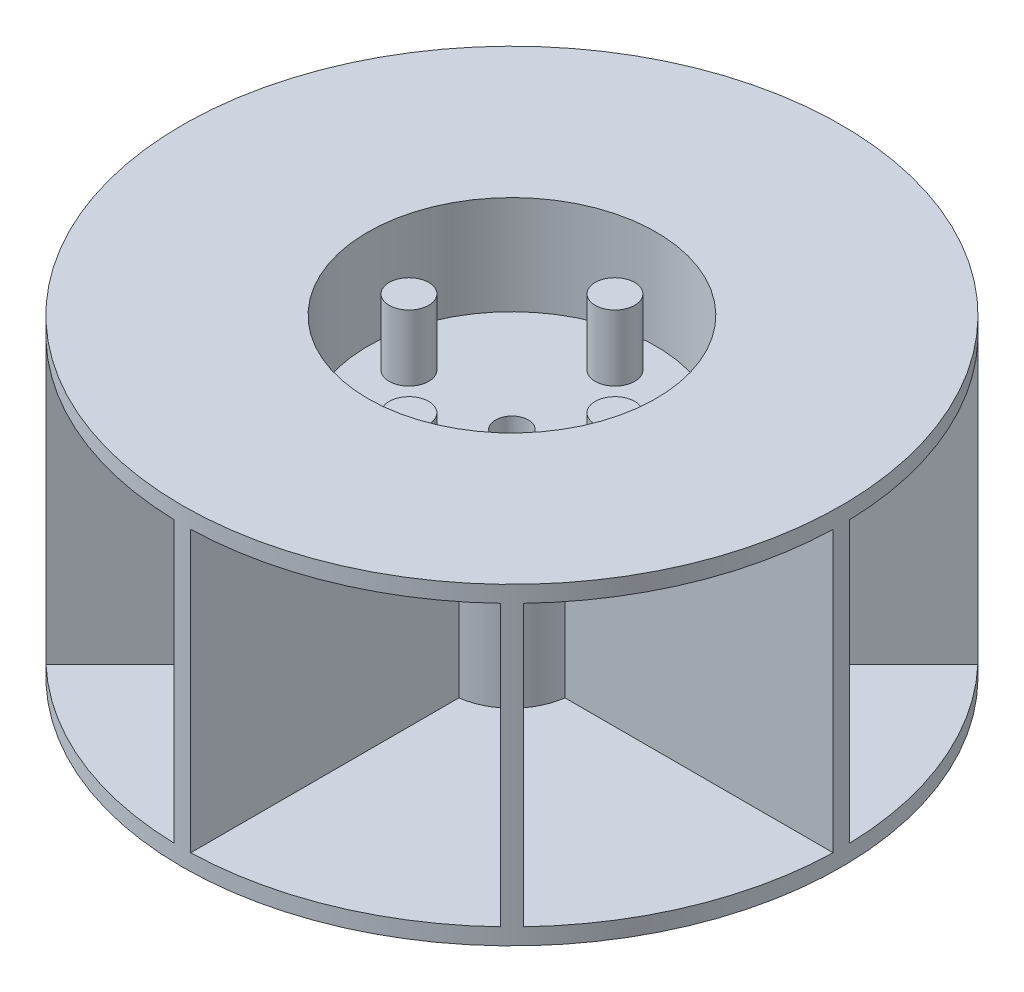
SolidWorks part; units mm, degrees
ref_plane "Front Plane" through (0, 0, 0) normal (0, 0, 1) x (1, 0, 0)
ref_plane "Top Plane" through (0, 0, 0) normal (0, 1, 0) x (1, 0, 0)
ref_plane "Right Plane" through (0, 0, 0) normal (1, 0, 0) x (0, 0, -1)
sketch "Sketch1" plane through (0, 0, 0) normal (0, 1, 0) x (1, 0, 0)
  circle A0 centre (0, 0) radius 3.175
  circle A1 centre (0, 0) radius 25.4
  dimension "D1" = 6.35
  dimension "D2" = 50.8
extrude "Boss-Extrude1" add sketch "Sketch1" along normal blind 1.27
sketch "Sketch2" plane through (0, 1.27, 0) normal (0, 1, 0) x (1, 0, 0)
  line L0 (0, 25.4) -> (0, 3.175)
  line L1 (-0.635, 25.3921) -> (-0.635, 3.1109)
  line L2 (0.635, 25.3921) -> (0.635, 3.1109)
  line L3 (18.4039, 17.5059) -> (2.6487, 1.7507)
  line L4 (17.5059, 18.4039) -> (1.7507, 2.6487)
  line L5 (25.3921, -0.635) -> (3.1109, -0.635)
  line L6 (25.3921, 0.635) -> (3.1109, 0.635)
  line L7 (17.5059, -18.4039) -> (1.7507, -2.6487)
  line L8 (18.4039, -17.5059) -> (2.6487, -1.7507)
  line L9 (-0.635, -25.3921) -> (-0.635, -3.1109)
  line L10 (0.635, -25.3921) -> (0.635, -3.1109)
  line L11 (-18.4039, -17.5059) -> (-2.6487, -1.7507)
  line L12 (-17.5059, -18.4039) -> (-1.7507, -2.6487)
  line L13 (-25.3921, 0.635) -> (-3.1109, 0.635)
  line L14 (-25.3921, -0.635) -> (-3.1109, -0.635)
  line L15 (-17.5059, 18.4039) -> (-1.7507, 2.6487)
  line L16 (-18.4039, 17.5059) -> (-2.6487, 1.7507)
  circle A0 centre (0, 0) radius 25.4 construction
  circle A1 centre (0, 0) radius 3.175 construction
  circle A2 centre (0, 0) radius 25.4
  circle A3 centre (0, 0) radius 3.175
  circle A4 centre (0, 0) radius 25.4 construction
  circle A5 centre (0, 0) radius 4.7625
  point P42 (0, 0)
  circle M4 centre (0, 0) radius 25.4
  circle M5 centre (0, 0) radius 3.175
  dimension "D1" = 0.635
  dimension "D4" = 9.525
  dimension "D3" = 8
  dimension "D2" = 0.635
extrude "Boss-Extrude4" add sketch "Sketch2" along normal blind 12.7 contours L1 L0 M4 M5 | L2 L0 M4 M5 | L4 L3 M4 M5 | L6 L5 M4 M5 | L8 L7 M4 M5 | L10 L9 M4 M5 | L12 L11 M4 M5 | L14 L13 M4 M5 | L16 L15 M4 M5 | L6 A5 L3 M5 | L5 A5 L6 M5 | L8 A5 L5 M5 | L7 A5 L8 M5 | L10 A5 L7 M5 | L9 A5 L10 M5 | L12 A5 L9 M5 | L11 A5 L12 M5 | L14 A5 L11 M5 | L13 A5 L14 M5 | L16 A5 L13 M5 | L15 A5 L16 M5 | L1 A5 L15 M5 | L0 A5 L1 M5 | L2 A5 L0 M5 | L4 A5 L2 M5 | L3 A5 L4 M5 region at (0.3176, 1.27, -15.0728) region at (-0.3176, 1.27, -15.0728) region at (0.3182, 1.27, -3.951) region at (-0.3182, 1.27, -3.951) region at (1.5388, 1.27, -3.7149) region at (-1.5388, 1.27, -3.7149) region at (10.6581, 1.27, -10.6581) region at (-10.6581, 1.27, -10.6581) region at (2.7938, 1.27, -2.7938) region at (-2.7938, 1.27, -2.7938) region at (3.7149, 1.27, -1.5388) region at (-3.7149, 1.27, -1.5388) region at (15.0728, 1.27, 0) region at (-15.0728, 1.27, 0) region at (3.951, 1.27, 0) region at (-3.951, 1.27, 0) region at (-3.7149, 1.27, 1.5388) region at (-10.6581, 1.27, 10.6581) region at (3.7149, 1.27, 1.5388) region at (-2.7938, 1.27, 2.7938) region at (10.6581, 1.27, 10.6581) region at (2.7938, 1.27, 2.7938) region at (-1.5388, 1.27, 3.7149) region at (0, 1.27, 15.0728) region at (1.5388, 1.27, 3.7149) region at (0, 1.27, 3.951)
sketch "Sketch5" plane through (0, 13.97, 0) normal (0, 1, 0) x (1, 0, 0)
  line L0 (0.635, -11.0943) -> (0.635, -25.3921)
  line L1 (0.635, -25.3921) -> (0.635, -4.72) construction
  line L2 (-0.635, -25.3921) -> (-0.635, -11.0943)
  line L3 (-0.635, -25.3921) -> (-0.635, -4.72) construction
  line L4 (-7.3959, -8.2939) -> (-17.5059, -18.4039)
  line L5 (-18.4039, -17.5059) -> (-8.2939, -7.3959)
  line L6 (-11.0943, -0.635) -> (-25.3921, -0.635)
  line L7 (-25.3921, 0.635) -> (-11.0943, 0.635)
  line L8 (-8.2939, 7.3959) -> (-18.4039, 17.5059)
  line L9 (-17.5059, 18.4039) -> (-7.3959, 8.2939)
  line L10 (-0.635, 11.0943) -> (-0.635, 25.3921)
  line L11 (0.635, 25.3921) -> (0.635, 11.0943)
  line L12 (7.3959, 8.2939) -> (17.5059, 18.4039)
  line L13 (18.4039, 17.5059) -> (8.2939, 7.3959)
  line L14 (11.0943, 0.635) -> (25.3921, 0.635)
  line L15 (25.3921, -0.635) -> (11.0943, -0.635)
  line L16 (8.2939, -7.3959) -> (18.4039, -17.5059)
  line L17 (17.5059, -18.4039) -> (7.3959, -8.2939)
  circle A0 centre (0, 0) radius 3.175
  circle A1 centre (0, 0) radius 11.1125
  circle A2 centre (0, 0) radius 25.4
  circle A3 centre (0, 0) radius 12.7
  point P45 (0, 0)
  circle M3 centre (0, 0) radius 3.175
  line M4 (17.5059, 18.4039) -> (2.8885, 3.7865)
  arc M5 (2.8885, 3.7865) -> (0.635, 4.72) centre (0, 0) ccw
  line M6 (0.635, 4.72) -> (0.635, 25.3921)
  arc M7 (0.635, 25.3921) -> (-0.635, 25.3921) centre (0, 0) ccw
  line M8 (-0.635, 25.3921) -> (-0.635, 4.72)
  arc M9 (-0.635, 4.72) -> (-2.8885, 3.7865) centre (0, 0) ccw
  line M10 (-2.8885, 3.7865) -> (-17.5059, 18.4039)
  arc M11 (-17.5059, 18.4039) -> (-18.4039, 17.5059) centre (0, 0) ccw
  line M12 (-18.4039, 17.5059) -> (-3.7865, 2.8885)
  arc M13 (-3.7865, 2.8885) -> (-4.72, 0.635) centre (0, 0) ccw
  line M14 (-4.72, 0.635) -> (-25.3921, 0.635)
  arc M15 (-25.3921, 0.635) -> (-25.3921, -0.635) centre (0, 0) ccw
  line M16 (-25.3921, -0.635) -> (-4.72, -0.635)
  arc M17 (-4.72, -0.635) -> (-3.7865, -2.8885) centre (0, 0) ccw
  line M18 (-3.7865, -2.8885) -> (-18.4039, -17.5059)
  arc M19 (-18.4039, -17.5059) -> (-17.5059, -18.4039) centre (0, 0) ccw
  line M20 (-17.5059, -18.4039) -> (-2.8885, -3.7865)
  arc M21 (-2.8885, -3.7865) -> (-0.635, -4.72) centre (0, 0) ccw
  line M22 (-0.635, -4.72) -> (-0.635, -25.3921)
  arc M23 (-0.635, -25.3921) -> (0.635, -25.3921) centre (0, 0) ccw
  line M24 (0.635, -25.3921) -> (0.635, -4.72)
  arc M25 (0.635, -4.72) -> (2.8885, -3.7865) centre (0, 0) ccw
  line M26 (2.8885, -3.7865) -> (17.5059, -18.4039)
  arc M27 (17.5059, -18.4039) -> (18.4039, -17.5059) centre (0, 0) ccw
  line M28 (18.4039, -17.5059) -> (3.7865, -2.8885)
  arc M29 (3.7865, -2.8885) -> (4.72, -0.635) centre (0, 0) ccw
  line M30 (4.72, -0.635) -> (25.3921, -0.635)
  arc M31 (25.3921, -0.635) -> (25.3921, 0.635) centre (0, 0) ccw
  line M32 (25.3921, 0.635) -> (4.72, 0.635)
  arc M33 (4.72, 0.635) -> (3.7865, 2.8885) centre (0, 0) ccw
  line M34 (3.7865, 2.8885) -> (18.4039, 17.5059)
  arc M35 (18.4039, 17.5059) -> (17.5059, 18.4039) centre (0, 0) ccw
  dimension "D1" = 22.225
  dimension "D3" = 1.5875
  dimension "D2" = 8
extrude "Boss-Extrude6" add sketch "Sketch5" along normal blind 2.54 contours A1 M28 M30 M29 | A1 M26 M28 M29 M30 M32 M33 M34 M4 M5 M6 M8 M9 M10 M12 M13 M14 M16 M17 M18 M20 M21 M22 M24 M25 M3 | A1 M24 M26 M25 | A1 M20 M22 M21 | A1 M16 M18 M17 | A1 M12 M14 M13 | A1 M8 M10 M9 | A1 M4 M6 M5 | A1 M32 M34 M33 region at (3.1868, 13.97, 7.6936) region at (0, 13.97, 10.7982) region at (-3.1868, 13.97, 7.6936) region at (7.6936, 13.97, 3.1868) region at (-7.6936, 13.97, 3.1868) region at (-7.6936, 13.97, -3.1868) region at (7.6936, 13.97, -3.1868) region at (-3.1868, 13.97, -7.6936) region at (3.1868, 13.97, -7.6936)
extrude "Boss-Extrude7" add sketch "Sketch5<4>" along normal blind 8.89 contours A1 M22 M23 M24 | A1 M26 M27 M28 | A1 M30 M31 M32 | A1 M34 M35 M4 | A1 M6 M7 M8 | A1 M10 M11 M12 | A1 M14 M15 M16 | A1 M18 M19 M20 | L16 A3 A1 M30 | A3 L16 A1 M26 | L0 A3 A1 M26 | A3 L0 A1 M22 | L4 A3 A1 M22 | A3 L4 A1 M18 | L6 A3 A1 M18 | A3 L6 A1 M14 | L8 A3 A1 M14 | A3 L8 A1 M10 | L10 A3 A1 M10 | A3 L10 A1 M6 | L12 A3 A1 M6 | A3 L12 A1 M34 | L14 A3 A1 M34 | A3 L14 A1 M30 region at (4.477, 13.97, 10.8084) region at (0, 13.97, 11.9006) region at (0, 13.97, 19.046) region at (-4.477, 13.97, 10.8084) region at (8.415, 13.97, 8.415) region at (13.4676, 13.97, 13.4676) region at (-8.415, 13.97, 8.415) region at (10.8084, 13.97, 4.477) region at (-13.4676, 13.97, 13.4676) region at (-10.8084, 13.97, 4.477) region at (11.9006, 13.97, 0) region at (19.046, 13.97, 0) region at (-11.9006, 13.97, 0) region at (-19.046, 13.97, 0) region at (-10.8084, 13.97, -4.477) region at (10.8084, 13.97, -4.477) region at (-8.415, 13.97, -8.415) region at (8.415, 13.97, -8.415) region at (-13.4676, 13.97, -13.4676) region at (13.4676, 13.97, -13.4676) region at (-4.477, 13.97, -10.8084) region at (4.477, 13.97, -10.8084) region at (0, 13.97, -11.9006) region at (0, 13.97, -19.046)
sketch "Sketch5<4>" plane through (0, 13.97, 0) normal (0, 1, 0) x (1, 0, 0) same geometry as "Sketch5"
sketch "Sketch6" plane through (0, 22.86, 0) normal (0, 1, 0) x (1, 0, 0)
  circle A0 centre (0, 0) radius 11.1125
  circle A1 centre (0, 0) radius 25.4
extrude "Boss-Extrude8" add sketch "Sketch6" along normal blind 1.27
sketch "Sketch7" plane through (0, 16.51, 0) normal (0, 1, 0) x (1, 0, 0)
  circle A0 centre (7.9375, 0) radius 1.524
  circle A1 centre (0, -7.9375) radius 1.524
  circle A2 centre (-7.9375, 0) radius 1.524
  circle A3 centre (0, 7.9375) radius 1.524
  point P12 (0, 0)
  dimension "D1" = 3.048
  dimension "D2" = 7.9375
  dimension "D3" = 4
extrude "Boss-Extrude9" add sketch "Sketch7" along normal blind 5.08
sketch "Sketch8" plane through (0, 16.51, 0) normal (0, 1, 0) x (1, 0, 0)
  circle A0 centre (0, 0) radius 3.175
  circle A1 centre (0, 0) radius 1.27
  circle A2 centre (0, 0) radius 3.175 construction
  dimension "D1" = 2.54
extrude "Boss-Extrude10" add sketch "Sketch8" against normal blind 1.5875
